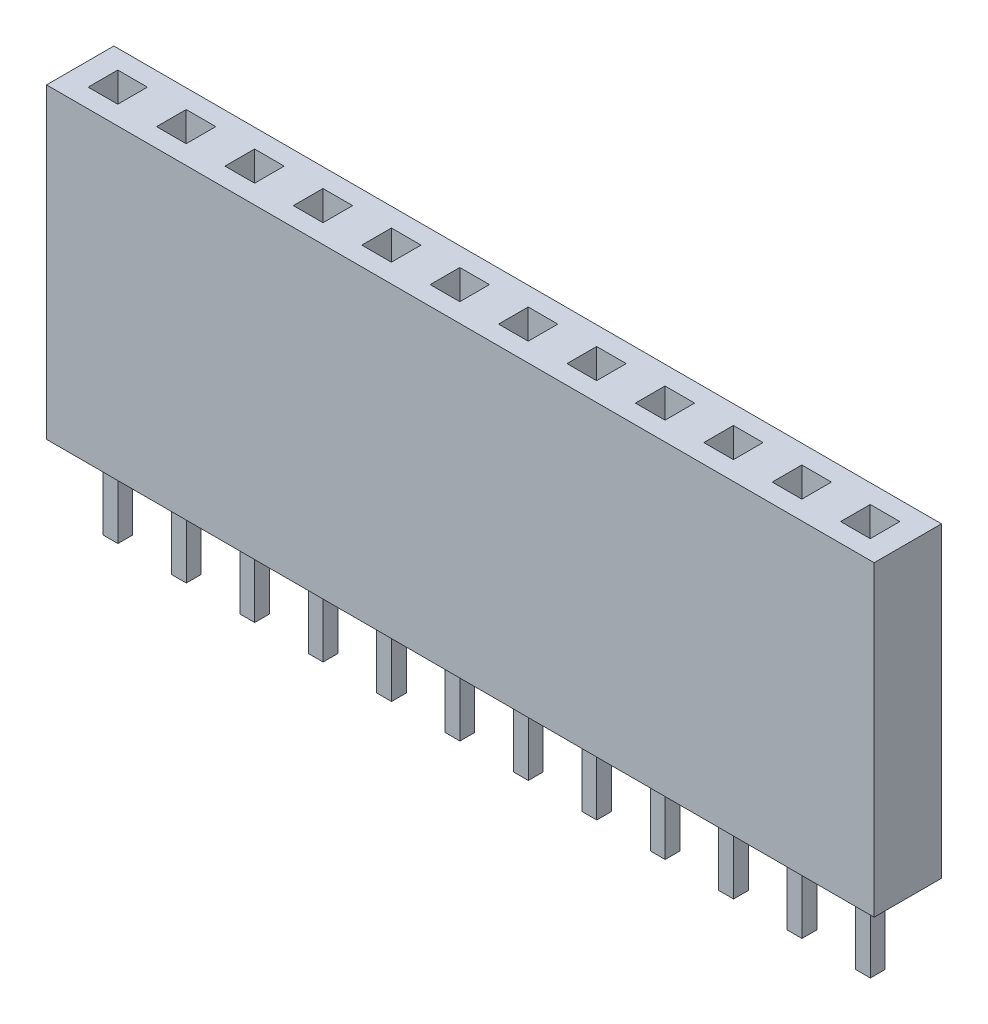
SolidWorks part; units mm, degrees
ref_plane "Front Plane" through (0, 0, 0) normal (0, 0, 1) x (1, 0, 0)
ref_plane "Top Plane" through (0, 0, 0) normal (0, 1, 0) x (1, 0, 0)
ref_plane "Right Plane" through (0, 0, 0) normal (1, 0, 0) x (0, 0, -1)
sketch "Sketch1" plane through (0, 0, 0) normal (0, 0, 1) x (1, 0, 0)
  line L1 (0, 0) -> (30.73, 0)
  line L2 (0, 0) -> (0, 11.4)
  line L3 (0, 11.4) -> (30.73, 11.4)
  line L4 (30.73, 0) -> (30.73, 11.4)
  dimension "D1" = 11.4
  dimension "D2" = 30.73
extrude "Boss-Extrude1" add sketch "Sketch1" along normal mid plane 2.5
sketch "Sketch2" plane through (0, 0, 0) normal (0, -1, 0) x (1, 0, 0)
  line L0 (0, 0) -> (30.73, 0) construction
  line L1 (30.73, 1.25) -> (30.73, -1.25) construction
  line L2 (3.385, -0.55) -> (4.485, -0.55)
  line L3 (0.845, -0.55) -> (1.945, -0.55)
  line L4 (0.845, -0.55) -> (0.845, 0.55)
  line L5 (0.845, 0.55) -> (1.945, 0.55)
  line L6 (1.945, -0.55) -> (1.945, 0.55)
  line L7 (0.845, -0.55) -> (1.945, 0.55) construction
  line L8 (0.845, 0.55) -> (1.945, -0.55) construction
  line L9 (3.385, -0.55) -> (3.385, 0.55)
  line L10 (3.385, 0.55) -> (4.485, 0.55)
  line L11 (4.485, -0.55) -> (4.485, 0.55)
  line L12 (3.385, -0.55) -> (4.485, 0.55) construction
  line L13 (3.385, 0.55) -> (4.485, -0.55) construction
  line L14 (5.925, -0.55) -> (7.025, -0.55)
  line L15 (5.925, -0.55) -> (5.925, 0.55)
  line L16 (5.925, 0.55) -> (7.025, 0.55)
  line L17 (7.025, -0.55) -> (7.025, 0.55)
  line L18 (5.925, -0.55) -> (7.025, 0.55) construction
  line L19 (5.925, 0.55) -> (7.025, -0.55) construction
  line L20 (8.465, -0.55) -> (9.565, -0.55)
  line L21 (8.465, -0.55) -> (8.465, 0.55)
  line L22 (8.465, 0.55) -> (9.565, 0.55)
  line L23 (9.565, -0.55) -> (9.565, 0.55)
  line L24 (8.465, -0.55) -> (9.565, 0.55) construction
  line L25 (8.465, 0.55) -> (9.565, -0.55) construction
  line L26 (11.005, -0.55) -> (12.105, -0.55)
  line L27 (11.005, -0.55) -> (11.005, 0.55)
  line L28 (11.005, 0.55) -> (12.105, 0.55)
  line L29 (12.105, -0.55) -> (12.105, 0.55)
  line L30 (11.005, -0.55) -> (12.105, 0.55) construction
  line L31 (11.005, 0.55) -> (12.105, -0.55) construction
  line L32 (13.545, -0.55) -> (14.645, -0.55)
  line L33 (13.545, -0.55) -> (13.545, 0.55)
  line L34 (13.545, 0.55) -> (14.645, 0.55)
  line L35 (14.645, -0.55) -> (14.645, 0.55)
  line L36 (13.545, -0.55) -> (14.645, 0.55) construction
  line L37 (13.545, 0.55) -> (14.645, -0.55) construction
  line L38 (16.085, -0.55) -> (17.185, -0.55)
  line L39 (16.085, -0.55) -> (16.085, 0.55)
  line L40 (16.085, 0.55) -> (17.185, 0.55)
  line L41 (17.185, -0.55) -> (17.185, 0.55)
  line L42 (16.085, -0.55) -> (17.185, 0.55) construction
  line L43 (16.085, 0.55) -> (17.185, -0.55) construction
  line L44 (18.625, -0.55) -> (19.725, -0.55)
  line L45 (18.625, -0.55) -> (18.625, 0.55)
  line L46 (18.625, 0.55) -> (19.725, 0.55)
  line L47 (19.725, -0.55) -> (19.725, 0.55)
  line L48 (18.625, -0.55) -> (19.725, 0.55) construction
  line L49 (18.625, 0.55) -> (19.725, -0.55) construction
  line L50 (21.165, -0.55) -> (22.265, -0.55)
  line L51 (21.165, -0.55) -> (21.165, 0.55)
  line L52 (21.165, 0.55) -> (22.265, 0.55)
  line L53 (22.265, -0.55) -> (22.265, 0.55)
  line L54 (21.165, -0.55) -> (22.265, 0.55) construction
  line L55 (21.165, 0.55) -> (22.265, -0.55) construction
  line L56 (23.705, -0.55) -> (24.805, -0.55)
  line L57 (23.705, -0.55) -> (23.705, 0.55)
  line L58 (23.705, 0.55) -> (24.805, 0.55)
  line L59 (24.805, -0.55) -> (24.805, 0.55)
  line L60 (23.705, -0.55) -> (24.805, 0.55) construction
  line L61 (23.705, 0.55) -> (24.805, -0.55) construction
  line L62 (26.245, -0.55) -> (27.345, -0.55)
  line L63 (26.245, -0.55) -> (26.245, 0.55)
  line L64 (26.245, 0.55) -> (27.345, 0.55)
  line L65 (27.345, -0.55) -> (27.345, 0.55)
  line L66 (26.245, -0.55) -> (27.345, 0.55) construction
  line L67 (26.245, 0.55) -> (27.345, -0.55) construction
  line L68 (28.785, -0.55) -> (29.885, -0.55)
  line L69 (28.785, -0.55) -> (28.785, 0.55)
  line L70 (28.785, 0.55) -> (29.885, 0.55)
  line L71 (29.885, -0.55) -> (29.885, 0.55)
  line L72 (28.785, -0.55) -> (29.885, 0.55) construction
  line L73 (28.785, 0.55) -> (29.885, -0.55) construction
  line L78 (1.395, 0) -> (3.935, 0) construction
  line L98 (31.325, -0.55) -> (32.425, -0.55) [skipped]
  line L99 (31.325, -0.55) -> (31.325, 0.55) [skipped]
  line L100 (31.325, 0.55) -> (32.425, 0.55) [skipped]
  line L101 (32.425, -0.55) -> (32.425, 0.55) [skipped]
  line L102 (33.865, -0.55) -> (34.965, -0.55) [skipped]
  line L103 (33.865, -0.55) -> (33.865, 0.55) [skipped]
  line L104 (33.865, 0.55) -> (34.965, 0.55) [skipped]
  line L105 (34.965, -0.55) -> (34.965, 0.55) [skipped]
  line L106 (36.405, -0.55) -> (37.505, -0.55) [skipped]
  line L107 (36.405, -0.55) -> (36.405, 0.55) [skipped]
  line L108 (36.405, 0.55) -> (37.505, 0.55) [skipped]
  line L109 (37.505, -0.55) -> (37.505, 0.55) [skipped]
  line L110 (38.945, -0.55) -> (40.045, -0.55) [skipped]
  line L111 (38.945, -0.55) -> (38.945, 0.55) [skipped]
  line L112 (38.945, 0.55) -> (40.045, 0.55) [skipped]
  line L113 (40.045, -0.55) -> (40.045, 0.55) [skipped]
  line L114 (31.325, -0.55) -> (32.425, 0.55) construction
  line L115 (31.325, 0.55) -> (32.425, -0.55) construction
  line L116 (33.865, -0.55) -> (34.965, 0.55) construction
  line L117 (33.865, 0.55) -> (34.965, -0.55) construction
  line L118 (36.405, -0.55) -> (37.505, 0.55) construction
  line L119 (36.405, 0.55) -> (37.505, -0.55) construction
  line L120 (38.945, -0.55) -> (40.045, 0.55) construction
  line L121 (38.945, 0.55) -> (40.045, -0.55) construction
  point P5 (1.395, 0)
  point P10 (36.955, 0)
  point P11 (34.415, 0)
  point P12 (3.935, 0)
  point P17 (6.475, 0)
  point P22 (9.015, 0)
  point P27 (11.555, 0)
  point P32 (14.095, 0)
  point P37 (16.635, 0)
  point P42 (19.175, 0)
  point P47 (21.715, 0)
  point P52 (24.255, 0)
  point P57 (26.795, 0)
  point P62 (29.335, 0)
  point P67 (39.495, 0)
  point P68 (31.875, 0)
  dimension "D1" = 1.1
  dimension "D3" = 1.395
  dimension "D4" = 2.54
  dimension "D2" = 16
extrude "Cut-Extrude1" cut sketch "Sketch2" against normal through all
sketch "Sketch3" plane through (0, 0, 0) normal (0, -1, 0) x (1, 0, 0)
  line L1 (0, 1.25) -> (30.73, 1.25)
  line L2 (0, 1.25) -> (0, -1.25)
  line L3 (0, -1.25) -> (30.73, -1.25)
  line L4 (30.73, 1.25) -> (30.73, -1.25)
extrude "Boss-Extrude2" add sketch "Sketch3" against normal blind 1
sketch "Sketch4" plane through (0, 0, 0) normal (0, -1, 0) x (1, 0, 0)
  line L0 (1.125, 0) -> (1.675, 0) construction
  line L1 (1.125, 0.275) -> (1.675, 0.275)
  line L2 (1.125, 0.275) -> (1.125, -0.275)
  line L3 (1.125, -0.275) -> (1.675, -0.275)
  line L4 (1.675, 0.275) -> (1.675, -0.275)
  line L5 (0, 0) -> (30.73, 0) construction
  line L6 (30.73, 1.25) -> (30.73, -1.25) construction
  line L7 (0, 1.25) -> (0, -1.25) construction
  line L8 (3.665, 0.275) -> (3.665, -0.275)
  line L9 (3.665, 0.275) -> (4.215, 0.275)
  line L10 (3.665, -0.275) -> (4.215, -0.275)
  line L11 (4.215, 0.275) -> (4.215, -0.275)
  line L12 (6.205, 0.275) -> (6.205, -0.275)
  line L13 (6.205, 0.275) -> (6.755, 0.275)
  line L14 (6.205, -0.275) -> (6.755, -0.275)
  line L15 (6.755, 0.275) -> (6.755, -0.275)
  line L16 (8.745, 0.275) -> (8.745, -0.275)
  line L17 (8.745, 0.275) -> (9.295, 0.275)
  line L18 (8.745, -0.275) -> (9.295, -0.275)
  line L19 (9.295, 0.275) -> (9.295, -0.275)
  line L20 (11.285, 0.275) -> (11.285, -0.275)
  line L21 (11.285, 0.275) -> (11.835, 0.275)
  line L22 (11.285, -0.275) -> (11.835, -0.275)
  line L23 (11.835, 0.275) -> (11.835, -0.275)
  line L24 (13.825, 0.275) -> (13.825, -0.275)
  line L25 (13.825, 0.275) -> (14.375, 0.275)
  line L26 (13.825, -0.275) -> (14.375, -0.275)
  line L27 (14.375, 0.275) -> (14.375, -0.275)
  line L28 (16.365, 0.275) -> (16.365, -0.275)
  line L29 (16.365, 0.275) -> (16.915, 0.275)
  line L30 (16.365, -0.275) -> (16.915, -0.275)
  line L31 (16.915, 0.275) -> (16.915, -0.275)
  line L32 (18.905, 0.275) -> (18.905, -0.275)
  line L33 (18.905, 0.275) -> (19.455, 0.275)
  line L34 (18.905, -0.275) -> (19.455, -0.275)
  line L35 (19.455, 0.275) -> (19.455, -0.275)
  line L36 (21.445, 0.275) -> (21.445, -0.275)
  line L37 (21.445, 0.275) -> (21.995, 0.275)
  line L38 (21.445, -0.275) -> (21.995, -0.275)
  line L39 (21.995, 0.275) -> (21.995, -0.275)
  line L40 (23.985, 0.275) -> (23.985, -0.275)
  line L41 (23.985, 0.275) -> (24.535, 0.275)
  line L42 (23.985, -0.275) -> (24.535, -0.275)
  line L43 (24.535, 0.275) -> (24.535, -0.275)
  line L44 (26.525, 0.275) -> (26.525, -0.275)
  line L45 (26.525, 0.275) -> (27.075, 0.275)
  line L46 (26.525, -0.275) -> (27.075, -0.275)
  line L47 (27.075, 0.275) -> (27.075, -0.275)
  line L48 (29.065, 0.275) -> (29.065, -0.275)
  line L49 (29.065, 0.275) -> (29.615, 0.275)
  line L50 (29.065, -0.275) -> (29.615, -0.275)
  line L51 (29.615, 0.275) -> (29.615, -0.275)
  line L52 (1.125, 0.275) -> (3.665, 0.275) construction
  point P6 (1.4, 0)
  dimension "D1" = 0.55
  dimension "D2" = 1.4
  dimension "D4" = 2.54
  dimension "D3" = 12
extrude "Boss-Extrude3" add sketch "Sketch4" along normal blind 3 separate body
ref_axis "Axis1" through (1.395, 0, 0) along (0, -1, 0)
ref_axis "Axis2" through (29.335, 0, 0) along (0, -1, 0)
